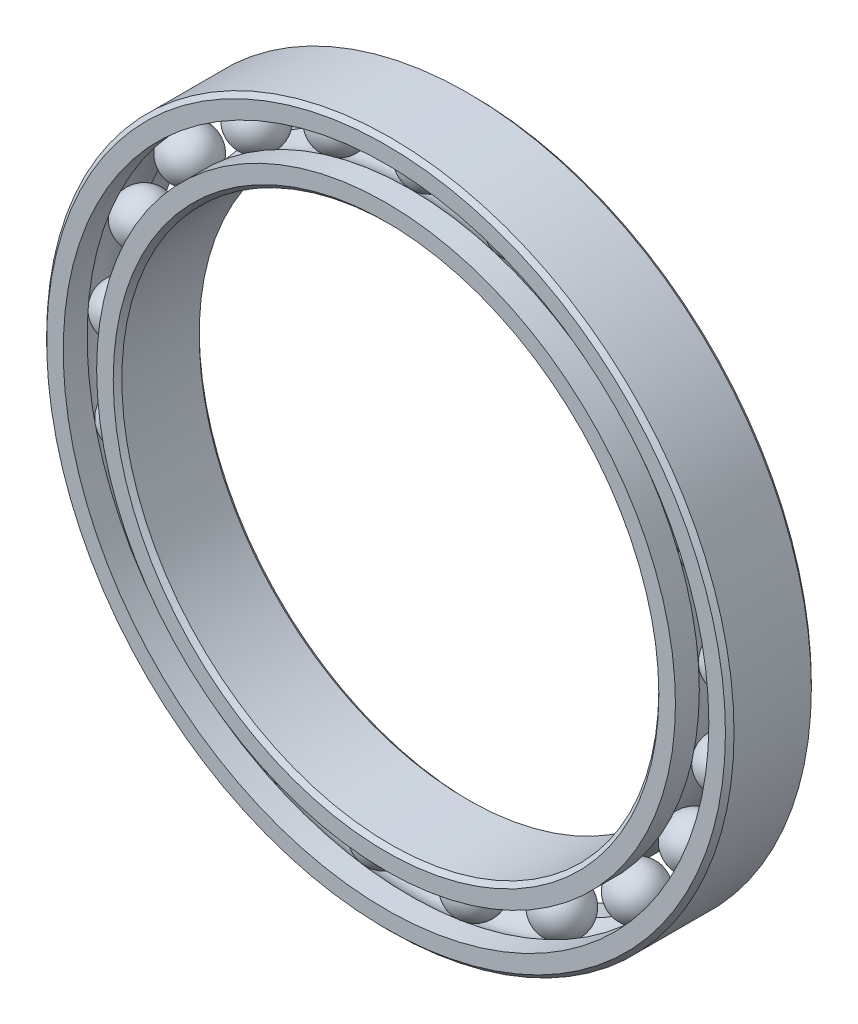
SolidWorks part; units mm, degrees
ref_plane "Front Plane" through (0, 0, 0) normal (0, 0, 1) x (1, 0, 0)
ref_plane "Top Plane" through (0, 0, 0) normal (0, 1, 0) x (1, 0, 0)
ref_plane "Right Plane" through (0, 0, 0) normal (1, 0, 0) x (0, 0, -1)
sketch "Sketch1" plane through (0, 0, 0) normal (0, 0, 1) x (1, 0, 0)
  circle A0 centre (0, 0) radius 16
  circle A1 centre (0, 0) radius 12.5
  dimension "OD" = 32
  dimension "ID" = 25
  dimension "For Shaft Diameter" = 25
  dimension "For Housing ID" = 32
sketch "Sketch5" plane through (0, 0, 0) normal (1, 0, 0) x (0, 0, -1)
  line L0 (-2, 0) -> (2, 0) construction
  line L1 (0, 16) -> (0, -16) construction
  line L2 (1.8, 16) -> (-1.8, 16)
  line L3 (-1.8, 16) -> (-2, 15.8)
  line L4 (-2, 15.8) -> (-2, 15.0278)
  line L5 (-2, 15.0278) -> (-0.8889, 15.0278)
  line L6 (2, 15.0278) -> (0.8889, 15.0278)
  line L7 (2, 15.8) -> (2, 15.0278)
  line L8 (1.8, 16) -> (2, 15.8)
  line L9 (0, 16) -> (0, 14.25) construction
  line L10 (0, 14.25) -> (0, 12.5) construction
  line L11 (-1.1811, 14.25) -> (-2, 14.25) construction
  line L12 (1.4001, 13.4976) -> (1.7811, 13.4976) construction
  line L13 (-1.4001, 13.4976) -> (-1.7811, 13.4976) construction
  line L14 (-1.4001, 13.4976) -> (-1.4001, 15.0024) construction
  line L15 (-1.4001, 15.0024) -> (-1.7811, 15.0024) construction
  line L16 (-1.7811, 13.4976) -> (-1.7811, 15.0024) construction
  line L17 (-1.4001, 13.4976) -> (-1.7811, 15.0024) construction
  line L18 (-1.4001, 15.0024) -> (-1.7811, 13.4976) construction
  line L19 (1.7811, 13.4976) -> (1.7811, 15.0024) construction
  line L20 (1.4001, 15.0024) -> (1.7811, 15.0024) construction
  line L21 (1.4001, 13.4976) -> (1.4001, 15.0024) construction
  line L22 (0, 16) -> (0, -16) construction
  arc A0 (-0.8889, 15.0278) -> (0.8889, 15.0278) centre (0, 14.25) cw
  circle A1 centre (0, 14.25) radius 1.1811 construction
  point P14 (0, 12.5)
  point P15 (-1.5906, 14.25)
  dimension "Width" = 4
  dimension "D1" = 45
  dimension "D2" = 0.2
  dimension "D3" = 1.7778
  dimension "D4" = 0.7778
  dimension "D5" = 0.381
  dimension "D6" = 0.0254
  dimension "D7" = 4
revolve "Revolve1" add sketch "Sketch5" angle 360 about L0
sketch "Sketch3" plane through (0, 0, 0) normal (1, 0, 0) x (0, 0, -1)
  line L0 (-2, 13.4722) -> (-0.8889, 13.4722)
  line L1 (0, 16) -> (0, -16) construction
  line L2 (-2, 15.8) -> (-2, 15.0278) construction
  line L3 (-2, 13.4722) -> (-2, 12.7)
  line L4 (-1.8, 16) -> (-2, 15.8) construction
  line L5 (-2, 12.7) -> (-1.8, 12.5)
  line L6 (-1.8, 12.5) -> (1.8, 12.5)
  line L7 (1.8, 16) -> (1.8, -16) construction
  line L8 (1.8, 12.5) -> (2, 12.7)
  line L9 (2, -15.8) -> (2, 15.8) construction
  line L10 (2, 12.7) -> (2, 13.4722)
  line L11 (2, 13.4722) -> (0.8889, 13.4722)
  line L13 (1.8, 16) -> (2, 15.8) construction
  arc A0 (0.8889, 15.0278) -> (-0.8889, 15.0278) centre (0, 14.25) ccw construction
  arc A1 (0.8889, 13.4722) -> (-0.8889, 13.4722) centre (0, 14.25) cw
revolve "Revolve3" add sketch "Sketch3" angle 360 about L0
sketch "Sketch4" plane through (0, 0, 0) normal (1, 0, 0) x (0, 0, -1)
  line L0 (-1.1811, 14.25) -> (1.1811, 14.25)
  arc A2 (-1.1811, 14.25) -> (1.1811, 14.25) centre (0, 14.25) cw
  arc A3 (0.8889, 15.0278) -> (-0.8889, 15.0278) centre (0, 14.25) ccw construction
revolve "Revolve4" add sketch "Sketch4" angle 360 about L0
pattern_circular "CirPattern1" count 21 every 17.143 of bodies 104
ref_axis "Center Axis 1" through (0, 0, -1.8) along (0, 0, 1)
ref_axis "Z" through (0, 0, -2.2) along (0, 0, 1)
equation "\"D2@Sketch5\" = \"Width@Sketch5\" * .05"
equation "\"D3@Sketch5\" = \"Width@Sketch5\" / 2.25"
equation "\"D4@Sketch5\"=((\"OD@Sketch1\"-\"ID@Sketch1\")/2)/4.5"
equation "\"D2@CirPattern1\" = 360/\"Balls@CirPattern1\""
